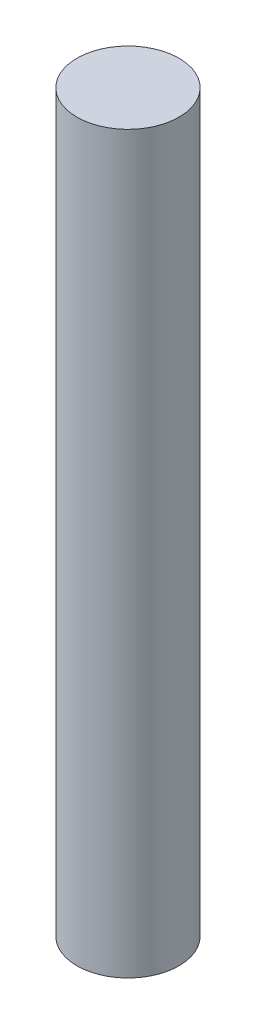
SolidWorks part; units mm, degrees
ref_plane "前视基准面" through (0, 0, 0) normal (0, 0, 1) x (1, 0, 0)
ref_plane "上视基准面" through (0, 0, 0) normal (0, 1, 0) x (1, 0, 0)
ref_plane "右视基准面" through (0, 0, 0) normal (1, 0, 0) x (0, 0, -1)
other "Configuration Table"
sketch "草图1" plane through (0, 0, 0) normal (0, 1, 0) x (1, 0, 0)
  circle A0 centre (0, 0) radius 5
  dimension "D1" = 10
extrude "凸台-拉伸1" add sketch "草图1" along normal blind 72
